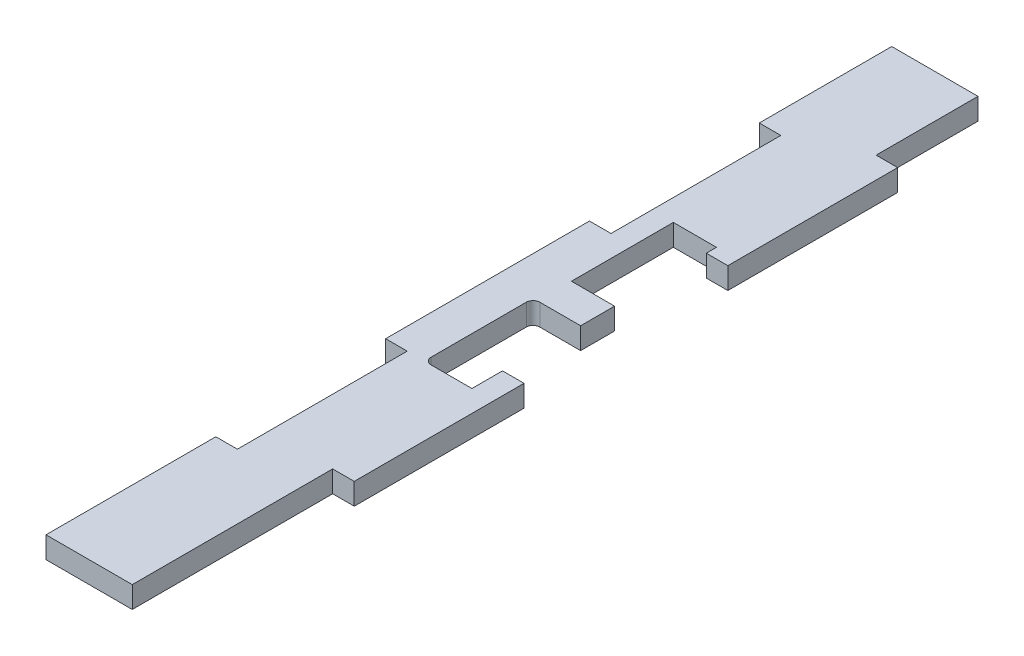
SolidWorks part; units mm, degrees
material "Balsa"
ref_plane "Front Plane" through (0, 0, 0) normal (0, 0, 1) x (1, 0, 0)
ref_plane "Top Plane" through (0, 0, 0) normal (0, 1, 0) x (1, 0, 0)
ref_plane "Right Plane" through (0, 0, 0) normal (1, 0, 0) x (0, 0, -1)
sketch "Sketch2" plane through (0, 0, 0) normal (0, 1, 0) x (1, 0, 0)
  line L13 (0, 0) -> (25.4, 0)
  line L14 (0, 0) -> (0, 249)
  line L15 (0, 249) -> (25.4, 249)
  line L16 (25.4, 0) -> (25.4, 59)
  line L17 (25.4, 59) -> (31.75, 59)
  line L19 (25.4, 109) -> (31.75, 109)
  line L20 (31.75, 59) -> (31.75, 109)
  line L21 (25.4, 169) -> (31.75, 169)
  line L22 (31.75, 169) -> (31.75, 219)
  line L23 (25.4, 219) -> (31.75, 219)
  line L25 (25.4, 219) -> (25.4, 249)
  line L26 (25.4, 109) -> (25.4, 169)
  dimension "D1" = 25.4
  dimension "D2" = 249
  dimension "D3" = 6.35
  dimension "D4" = 50
  dimension "D5" = 59
  dimension "D6" = 2
  dimension "D7" = 30
extrude "Boss-Extrude1" add sketch "Sketch2" along normal blind 6.35
sketch "Sketch3" plane through (0, 6.35, 0) normal (0, 1, 0) x (1, 0, 0)
  line L5 (25.4, 109) -> (25.4, 169) construction
  line L6 (25.4, 132) -> (11.4, 132)
  line L7 (25.4, 132) -> (25.4, 100)
  line L8 (25.4, 100) -> (11.4, 100)
  line L9 (11.4, 132) -> (11.4, 100)
  line L10 (0, 0) -> (25.4, 0) construction
  line L12 (25.4, 142) -> (12.7, 142)
  line L13 (25.4, 142) -> (25.4, 172)
  line L14 (25.4, 172) -> (12.7, 172)
  line L15 (12.7, 142) -> (12.7, 172)
  dimension "D4" = 30
  dimension "D1" = 100
  dimension "D2" = 14
  dimension "D3" = 32
  dimension "D5" = 12.7
  dimension "D6" = 10
extrude "Cut-Extrude1" cut sketch "Sketch3" against normal through all
fillet "Fillet1" radius 2 2 edges at (11.4, 3.175, -100) (11.4, 3.175, -132)
sketch "Sketch4" plane through (0, 6.35, 0) normal (0, 1, 0) x (1, 0, 0)
  line L0 (0, 249) -> (0, 0) construction
  line L1 (0, 50) -> (6.35, 50)
  line L2 (0, 50) -> (0, 100)
  line L3 (0, 100) -> (6.35, 100)
  line L4 (6.35, 50) -> (6.35, 100)
  line L5 (0, 0) -> (25.4, 0) construction
  line L6 (0, 160) -> (0, 210)
  line L7 (0, 160) -> (6.35, 160)
  line L8 (6.35, 160) -> (6.35, 210)
  line L9 (0, 210) -> (6.35, 210)
  line L10 (25.4, 249) -> (0, 249) construction
  dimension "D1" = 6.35
  dimension "D2" = 50
  dimension "D3" = 50
  dimension "D5" = 39
  dimension "D4" = 2
extrude "Cut-Extrude2" cut sketch "Sketch4" against normal through all
